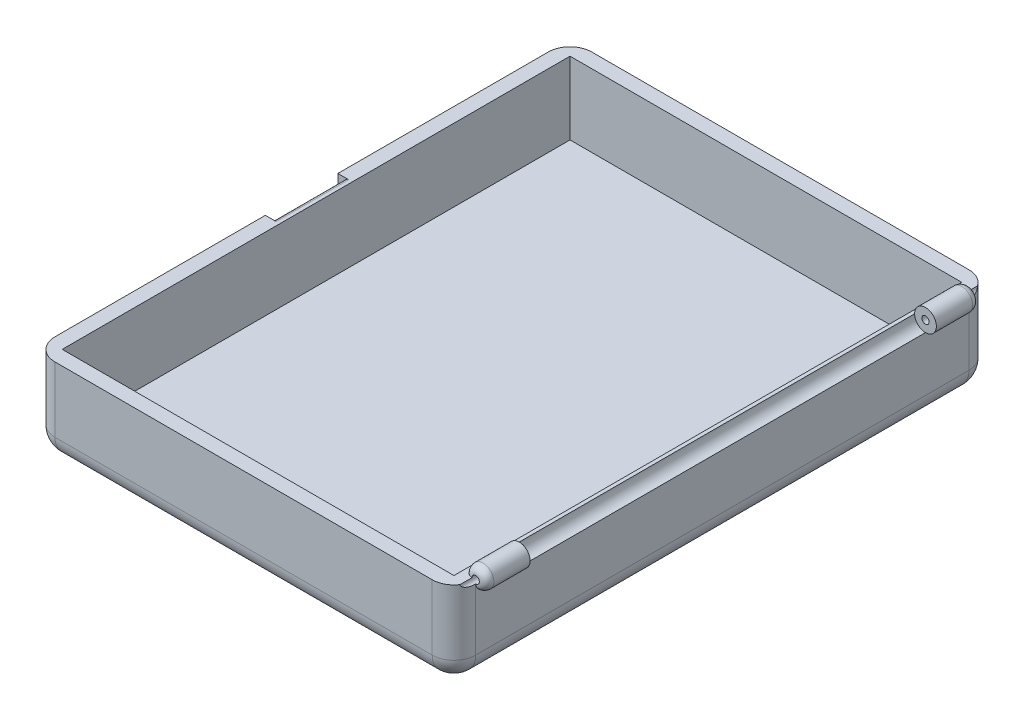
SolidWorks part; units mm, degrees
ref_plane "Front Plane" through (0, 0, 0) normal (0, 0, 1) x (1, 0, 0)
ref_plane "Top Plane" through (0, 0, 0) normal (0, 1, 0) x (1, 0, 0)
ref_plane "Right Plane" through (0, 0, 0) normal (1, 0, 0) x (0, 0, -1)
sketch "bottom" plane through (0, 0, 0) normal (0, 1, 0) x (1, 0, 0)
  line L0 (-2, 72) -> (56, 72)
  line L1 (0, 0) -> (54, 0)
  line L2 (0, 0) -> (0, 70)
  line L3 (0, 70) -> (54, 70)
  line L4 (54, 0) -> (54, 70)
  line L5 (56, -2) -> (56, 72)
  line L6 (-2, -2) -> (56, -2)
  line L7 (-2, -2) -> (-2, 72)
  dimension "D1" = 54
  dimension "D2" = 70
  dimension "D3" = 2
extrude "duvar" add sketch "bottom" along normal blind 12
extrude "taban" add sketch "bottom<2>" along normal blind 2 contours L1 L4 L3 L2 region at (27, 0, -35)
sketch "bottom<2>" plane through (0, 0, 0) normal (0, 1, 0) x (1, 0, 0) same geometry as "bottom"
fillet "Fillet2" radius 3 8 edges at (-2, 6, 2) (-2, 0, -35) (-2, 6, -72) (27, 0, -72) (56, 6, -72) (27, 0, 2) (56, 0, -35) (56, 6, 2)
ref_plane "mentese panel 1" through (0, 0, -1) normal (0, 0, 1) x (1, 0, 0)
ref_plane "mentese panel 2" through (0, 0, -69) normal (0, 0, -1) x (-1, 0, 0)
sketch "mentese out" plane through (0, 0, -69) normal (0, 0, -1) x (-1, 0, 0)
  circle A0 centre (-56, 12) radius 1.5
  dimension "D1" = 3
sketch "mentese in" plane through (0, 0, -1) normal (0, 0, 1) x (1, 0, 0)
  circle A0 centre (56, 12) radius 0.5
  dimension "D1" = 1
extrude "mentese" add sketch "mentese out" against normal blind 68
extrude "mentese delik" cut sketch "mentese in" against normal through all and the other way through all
fillet "mentese fillet" radius 1 2 edges at (57.0607, 13.0607, -69) (57.0607, 13.0607, -1)
ref_plane "mentese panel 3" through (0, 0, -7) normal (0, 0, 1) x (1, 0, 0)
ref_plane "mentese panel 4" through (0, 0, -63) normal (0, 0, -1) x (-1, 0, 0)
sketch "mentese out cut" plane through (0, 0, -63) normal (0, 0, -1) x (-1, 0, 0)
  circle A0 centre (-56, 12) radius 1.5
extrude "mentese bosluk" cut sketch "mentese out cut" against normal blind 56
sketch "centik" plane through (0, 12, 0) normal (0, 1, 0) x (1, 0, 0)
  line L0 (-2, 69) -> (-2, 1) construction
  line L1 (-2, 40) -> (-0.5, 40)
  line L2 (-2, 40) -> (-2, 30)
  line L3 (-2, 30) -> (-0.5, 30)
  line L4 (-0.5, 40) -> (-0.5, 30)
  point P7 (-2, 35)
  dimension "D1" = 10
  dimension "D2" = 1.5
  dimension "D3" = 5
extrude "centik bosluk" cut sketch "centik" against normal blind 7
sketch "dil" plane through (0, 0, -40) normal (0, 0, 1) x (1, 0, 0)
  circle A0 centre (-0.5, 11.5) radius 0.5
  dimension "D1" = 1
extrude "Boss-Extrude5" add sketch "dil" along normal blind 10
